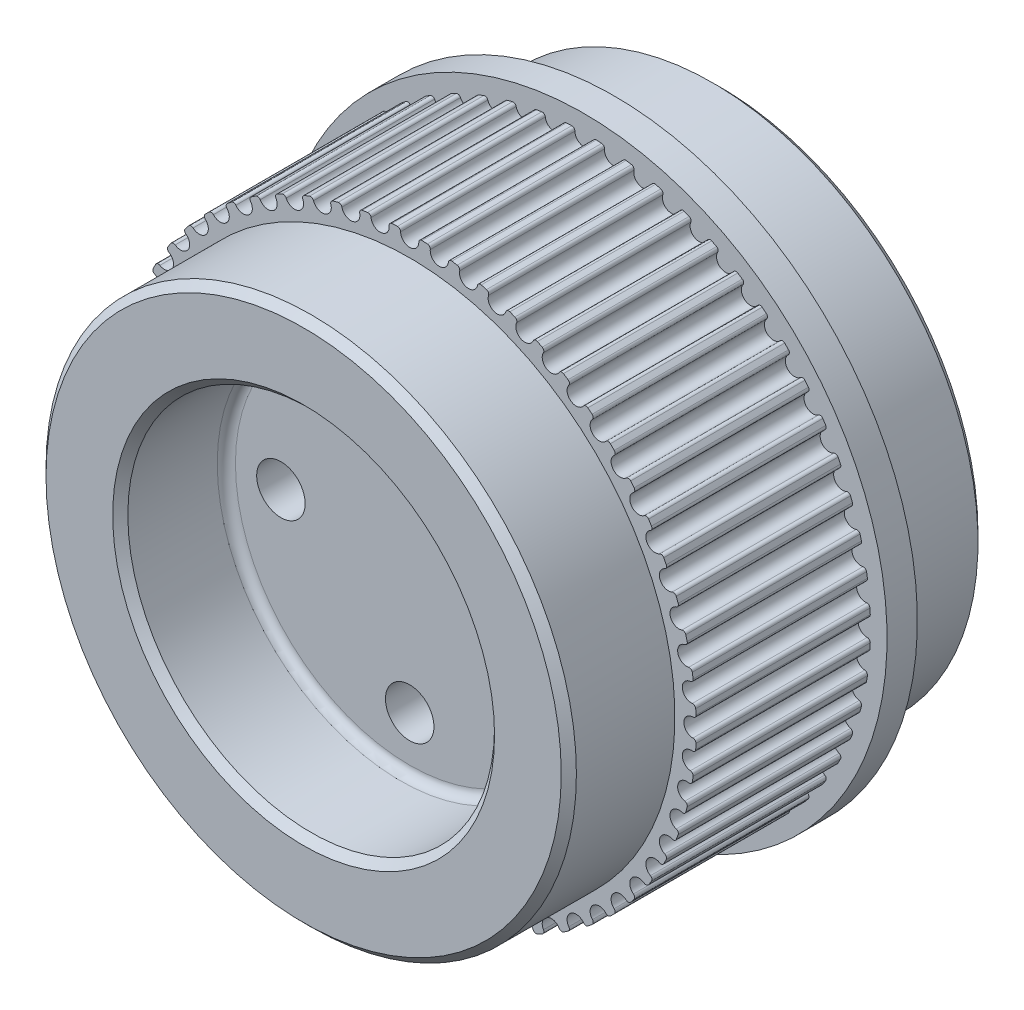
SolidWorks part; units mm, degrees
ref_plane "Front Plane" through (0, 0, 0) normal (0, 0, 1) x (1, 0, 0)
ref_plane "Top Plane" through (0, 0, 0) normal (0, 1, 0) x (1, 0, 0)
ref_plane "Right Plane" through (0, 0, 0) normal (1, 0, 0) x (0, 0, -1)
ref_axis "Axis1" through (0, 0, 55) along (0, 0, -1)
sketch "SketchRevolveGearBelt02" plane through (0, 0, 0) normal (1, 0, 0) x (0, 0, -1)
  line L0 (0, 0) -> (1, 0) construction
  line L1 (11.5, 0) -> (11.5, 18.9081)
  line L2 (11.5, 18.9081) -> (0, 18.9081)
  line L3 (0, 18.9081) -> (0, 0)
  line L4 (0, 0) -> (11.5, 0)
  dimension "GearBeltSide1" = 11.5
  dimension "GearBeltOutsideDiameter" = 18.9081
revolve "GearBelt02" add sketch "SketchRevolveGearBelt02" angle 360 about L0
sketch "SketchToothGearBelt02" plane through (0, 0, 0) normal (0, 0, 1) x (1, 0, 0)
  line L0 (-0.8105, 18.8907) -> (0, 21.4481)
  line L1 (0, 21.4481) -> (0.8105, 18.8907)
  arc A0 (0.8105, 18.8907) -> (0.6, 18.6891) centre (0.8018, 18.6891) ccw
  arc A1 (0.6, 18.6891) -> (-0.6, 18.6891) centre (0, 18.6891) cw
  arc A2 (-0.6, 18.6891) -> (-0.8105, 18.8907) centre (-0.8018, 18.6891) ccw
  dimension "GearBeltToothR1" = 0.4036
  dimension "GearBeltToothR2" = 1.2
  dimension "GearBeltToothCapX1" = 0.8105
  dimension "GearBeltToothCapY1" = 2.5574
  dimension "GearBeltToothCapX2" = 0.8105
  dimension "GearBeltToothCapY2" = 2.5574
extrude "ToothExtrudeCutGearBelt02" cut sketch "SketchToothGearBelt02" against normal blind 11.5
pattern_circular "PatternGearBelt02" count 60 every 6 about axis through (0, 0, 55) along (0, 0, -1) of "ToothExtrudeCutGearBelt02"
sketch "Эскиз2" plane through (0, 0, -11.5) normal (0, 0, -1) x (-1, 0, 0)
  circle A0 centre (0, 0) radius 20
  dimension "D1" = 40
extrude "Бобышка-Вытянуть1" add sketch "Эскиз2" along normal blind 2
sketch "Эскиз7" plane through (0, 0, 0) normal (0, 0, 1) x (1, 0, 0)
  circle A0 centre (0, 0) radius 12.1
  circle A1 centre (0, 0) radius 17.5
  dimension "D1" = 35
  dimension "D2" = 24.2
extrude "Бобышка-Вытянуть2" add sketch "Эскиз7" along normal blind 7
sketch "Эскиз8" plane through (0, 0, -13.5) normal (0, 0, -1) x (-1, 0, 0)
  circle A0 centre (0, 0) radius 17.5
  dimension "D1" = 35
extrude "Бобышка-Вытянуть3" add sketch "Эскиз8" along normal blind 7
chamfer "Фаска1" distance 0.5 angle 45 3 edges at (-17.5, 0, -20.5) (17.5, 0, 7) (12.1, 0, 7)
sketch "Эскиз5" plane through (0, 0, -20.5) normal (0, 0, 1) x (1, 0, 0)
  circle A0 centre (0, 0) radius 8.5 construction
  circle A1 centre (0, 8.5) radius 1.6
  circle A4 centre (0, 8.5) radius 3.25
  circle A5 centre (8.5, 0) radius 1.6
  circle A6 centre (8.5, 0) radius 3.25
  circle A7 centre (0, -8.5) radius 1.6
  circle A8 centre (0, -8.5) radius 3.25
  circle A9 centre (-8.5, 0) radius 1.6
  circle A10 centre (-8.5, 0) radius 3.25
  point P18 (0, 0)
  dimension "D1" = 3.2
  dimension "D2" = 17
  dimension "D3" = 6.5
  dimension "D4" = 4
extrude "Вырез-Вытянуть2" cut sketch "Эскиз5" along normal through all contours A5 | A1 | A9 | A7
extrude "Вырез-Вытянуть3" cut sketch "Эскиз5<4>" along normal blind 4
sketch "Эскиз5<4>" plane through (0, 0, -20.5) normal (0, 0, 1) x (1, 0, 0) same geometry as "Эскиз5"
sketch "Эскиз9" plane through (0, 0, -20.5) normal (0, 0, -1) x (-1, 0, 0)
  circle A0 centre (0, 0) radius 3
  dimension "D1" = 6
extrude "Вырез-Вытянуть4" cut sketch "Эскиз9" against normal blind 4
chamfer "Фаска2" distance 0.3 angle 45 1 edges at (-3, 0, -20.5)
fillet "Скругление1" radius 0.6 1 edges at (12.1, 0, 0)
